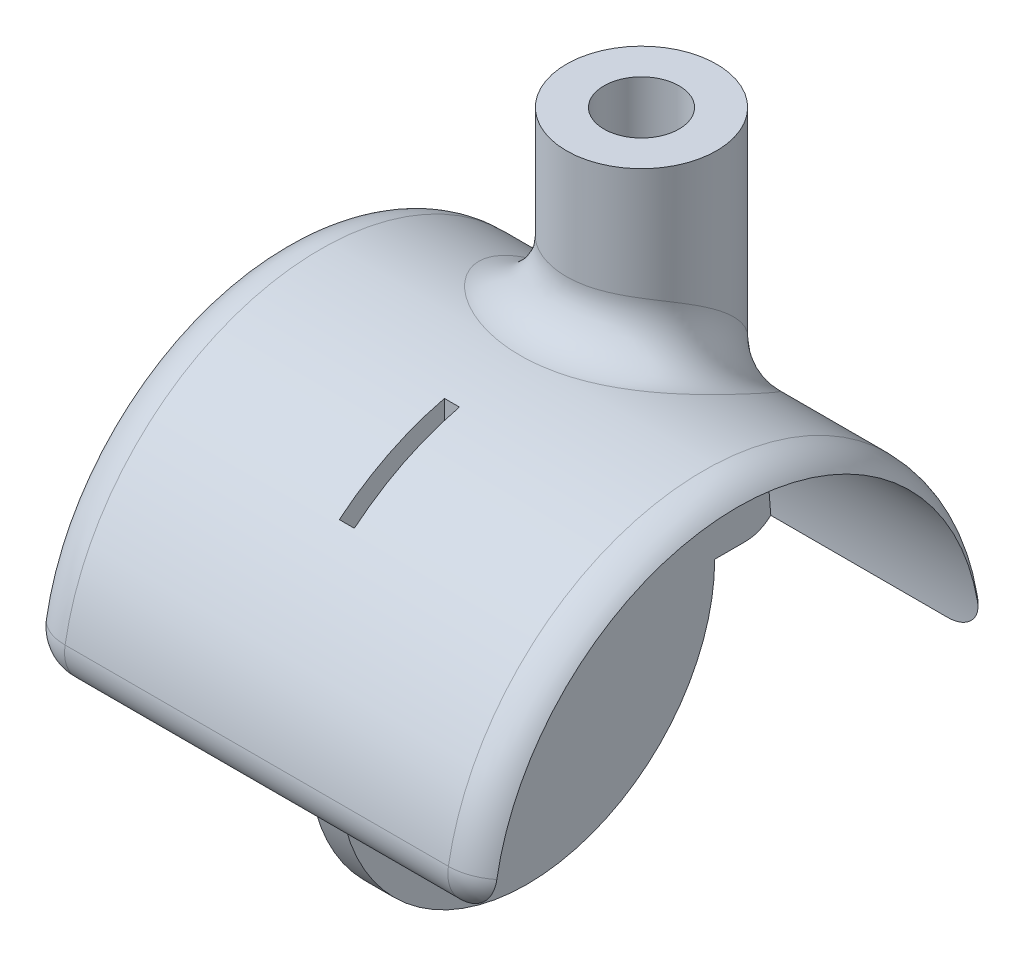
SolidWorks part; units mm, degrees
material "PE High Density"
ref_plane "Front Plane" through (0, 0, 0) normal (0, 0, 1) x (1, 0, 0)
ref_plane "Top Plane" through (0, 0, 0) normal (0, 1, 0) x (1, 0, 0)
ref_plane "Right Plane" through (0, 0, 0) normal (1, 0, 0) x (0, 0, -1)
sketch "Sketch1" plane through (0, 0, 0) normal (1, 0, 0) x (0, 0, -1)
  line L0 (0, 0) -> (34.5, 0) construction
  line L1 (0, 0) -> (-34.5, 0) construction
  line L2 (0, 0) -> (0, 34.5) construction
  line L3 (-34.5, 0) -> (-32.5, 0)
  line L4 (34.5, 0) -> (32.5, 0)
  arc A0 (32.5, 0) -> (-32.5, 0) centre (0, 0) ccw
  arc A1 (34.5, 0) -> (-34.5, 0) centre (0, 0) ccw
  dimension "D1" = 65
  dimension "D2" = 2
  dimension "D3" = 90
  dimension "D4" = 90
extrude "Boss-Extrude1" add sketch "Sketch1" along normal mid plane 60
sketch "Sketch2" plane through (0, 0, 0) normal (1, 0, 0) x (0, 0, -1)
  line L0 (-32.5, 0) -> (-25, 0)
  line L1 (32.5, 0) -> (25, 0)
  arc A0 (-25, 0) -> (25, 0) centre (0, 0) ccw
  arc A1 (32.5, 0) -> (-32.5, 0) centre (0, 0) ccw
  circle A2 centre (0, 0) radius 5
  dimension "D1" = 50
  dimension "D2" = 10
extrude "Boss-Extrude2" add sketch "Sketch2" along normal mid plane 4
ref_plane "Plane1" through (0, 55, 0) normal (0, 1, 0) x (1, 0, 0)
sketch "Sketch3" plane through (0, 55, 0) normal (0, 1, 0) x (1, 0, 0)
  line L0 (0, 0) -> (0, 34.5) construction
  line L1 (30, 34.5) -> (-30, 34.5) construction
  circle A0 centre (0, 17.25) radius 10
  circle A1 centre (0, 17.25) radius 5
  dimension "D1" = 20
  dimension "D2" = 10
extrude "Boss-Extrude3" add sketch "Sketch3" against normal up to surface (21.2704 mm away) contours A0 | A1 up to face at (0, 17.25, 0)
fillet "Fillet1" radius 6 1 edges at (0.3259, 21.1655, -27.2447)
fillet "Fillet2" radius 6 2 edges at (-30, 34.5, 0) (30, 34.5, 0)
fillet "Fillet3" radius 5 5 edges at (-16, 0, 32.5) (0, 0, 34.5) (27.9774, 0, 33.9772) (-27.9774, 0, 33.9772) (16, 0, 32.5)
fillet "Fillet4" radius 5 5 edges at (-16, 0, -32.5) (0, 0, -34.5) (27.9774, 0, -33.9772) (-27.9774, 0, -33.9772) (16, 0, -32.5)
sketch "Sketch4" plane through (0, 55, 0) normal (0, 1, 0) x (1, 0, 0)
  line L0 (0, 0) -> (0, -34.0732) construction
  line L1 (-25.5279, -34.0732) -> (25.5279, -34.0732) construction
  line L3 (-1, -8) -> (1, -8)
  line L4 (-1, -8) -> (-1, -22)
  line L5 (-1, -22) -> (1, -22)
  line L6 (1, -8) -> (1, -22)
  line L7 (-1, -8) -> (1, -22) construction
  line L8 (-1, -22) -> (1, -8) construction
  point P5 (0, -15)
  dimension "D1" = 15
  dimension "D2" = 2
  dimension "D3" = 14
extrude "Cut-Extrude1" cut sketch "Sketch4" against normal blind 34
